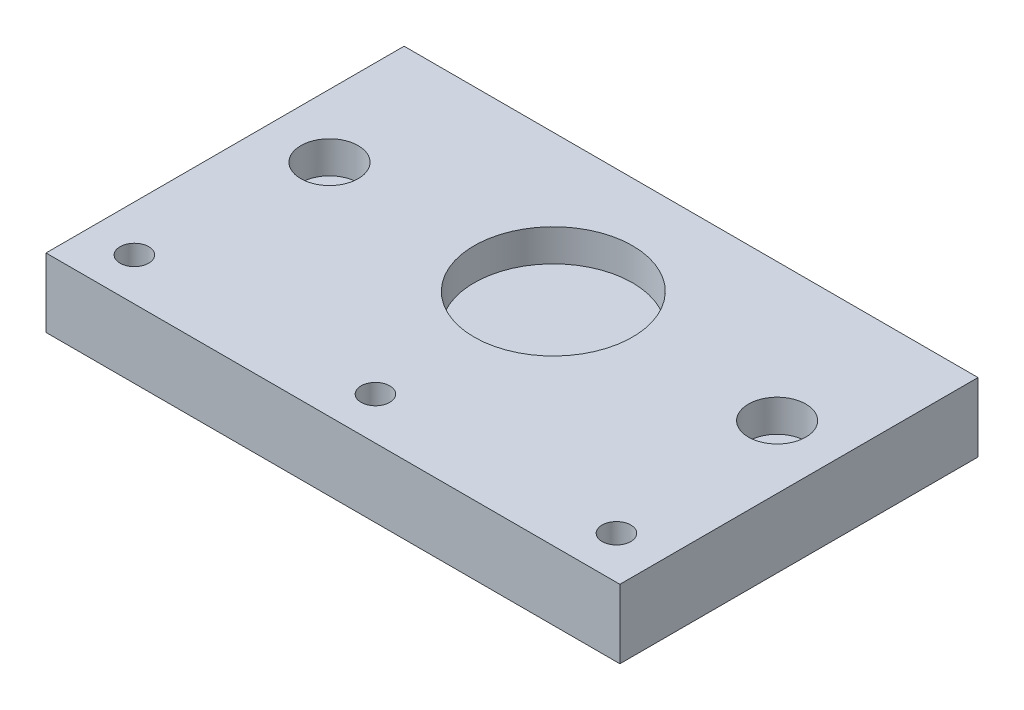
SolidWorks part; units mm, degrees
ref_plane "Front Plane" through (0, 0, 0) normal (0, 0, 1) x (1, 0, 0)
ref_plane "Top Plane" through (0, 0, 0) normal (0, 1, 0) x (1, 0, 0)
ref_plane "Right Plane" through (0, 0, 0) normal (1, 0, 0) x (0, 0, -1)
sketch "Sketch1" plane through (0, 0, 0) normal (0, 0, 1) x (1, 0, 0)
  line L1 (-31.75, 12.7) -> (31.75, 12.7)
  line L2 (-31.75, 12.7) -> (-31.75, -12.7)
  line L3 (-31.75, -12.7) -> (31.75, -12.7)
  line L4 (31.75, 12.7) -> (31.75, -12.7)
  point P4 (-31.75, 0)
  point P6 (0, 12.7)
  dimension "D1" = 63.5
  dimension "D2" = 25.4
extrude "Boss-Extrude1" add sketch "Sketch1" along normal blind 38.1
sketch "Sketch2" plane through (0, -12.7, 0) normal (0, -1, 0) x (1, 0, 0)
  line L0 (0, 0) -> (0, 102.7115) construction
  line L1 (-31.75, 0) -> (31.75, 0) construction
  circle A0 centre (24.765, 15.24) radius 3.175
  circle A1 centre (0, 15.24) radius 8.763
  circle A2 centre (-24.765, 15.24) radius 3.175
  dimension "D1" = 17.526
  dimension "D2" = 6.35
  dimension "D3" = 6.35
  dimension "D4" = 15.24
  dimension "D5" = 15.24
  dimension "D6" = 49.53
extrude "Cut-Extrude1" cut sketch "Sketch2" against normal blind 12.7 contours A2 | A0 region at (-24.765, -12.7, 15.24)
extrude "Cut-Extrude2" cut sketch "Sketch2<3>" against normal blind 4.826 contours A1
sketch "Sketch2<3>" plane through (0, -12.7, 0) normal (0, -1, 0) x (1, 0, 0) same geometry as "Sketch2"
sketch "Sketch3" plane through (0, -7.874, 0) normal (0, -1, 0) x (1, 0, 0)
  circle A0 centre (0, 15.24) radius 6.35
  dimension "D1" = 12.7
extrude "Cut-Extrude3" cut sketch "Sketch3" against normal up to vertex (20.574 mm away) up to point (31.75, 12.7, 0)
sketch "Sketch4" plane through (0, 12.7, 0) normal (0, 1, 0) x (1, 0, 0)
  line L0 (31.75, 0) -> (-31.75, 0) construction
  circle A0 centre (0, -15.24) radius 10.795
  point P6 (0, 0)
  dimension "D1" = 21.59
extrude "Cut-Extrude4" cut sketch "Sketch4" against normal blind 19.05
sketch "Sketch5" plane through (0, 12.7, 0) normal (0, 1, 0) x (1, 0, 0)
  line L0 (31.75, -38.1) -> (-31.75, -38.1) construction
  circle A0 centre (-26.67, -34.925) radius 1.5875
  circle A1 centre (0, -34.925) radius 1.5875
  circle A2 centre (26.67, -34.925) radius 1.5875
  dimension "D1" = 3.175
  dimension "D2" = 53.34
  dimension "D3" = 26.67
  dimension "D4" = 3.175
extrude "Cut-Extrude5" cut sketch "Sketch5" against normal blind 50.8
sketch "Sketch6" plane through (0, 0, 38.1) normal (0, 0, 1) x (1, 0, 0)
  line L0 (31.75, -12.7) -> (31.75, 12.7) construction
  line L1 (-31.75, -12.7) -> (31.75, -12.7)
  line L2 (-31.75, -12.7) -> (-31.75, -11.43)
  line L3 (-31.75, -11.43) -> (31.75, -11.43)
  line L4 (31.75, -12.7) -> (31.75, -11.43)
  dimension "D1" = 1.27
extrude "Cut-Extrude6" cut sketch "Sketch6" against normal up to vertex (38.1 mm away) up to point (-31.75, -12.7, 0)
sketch "Sketch7" plane through (0, 0, 38.1) normal (0, 0, 1) x (1, 0, 0)
  line L4 (-31.75, -11.43) -> (31.75, -11.43)
  line L5 (31.75, -11.43) -> (31.75, 12.7)
  line L6 (31.75, 12.7) -> (-31.75, 12.7)
  line L7 (-31.75, 12.7) -> (-31.75, -11.43)
  line L8 (-31.75, -11.43) -> (31.75, -11.43)
  line L9 (31.75, -11.43) -> (31.75, 12.7)
  line L10 (31.75, 12.7) -> (-31.75, 12.7)
  line L11 (-31.75, 12.7) -> (-31.75, -11.43)
  dimension "D1" = 0
extrude "Boss-Extrude2" add sketch "Sketch7" along normal blind 1.524
sketch "Sketch8" plane through (0, -6.35, 0) normal (0, 1, 0) x (1, 0, 0)
  line L1 (-42.4868, 12.7569) -> (52.6567, 12.7569)
  line L2 (-42.4868, 12.7569) -> (-42.4868, -56.416)
  line L3 (-42.4868, -56.416) -> (52.6567, -56.416)
  line L4 (52.6567, 12.7569) -> (52.6567, -56.416)
extrude "Cut-Extrude7" cut sketch "Sketch8" along normal through all
sketch "Sketch9" plane through (0, -11.43, 0) normal (0, -1, 0) x (1, 0, 0)
  line L4 (31.75, 0) -> (31.75, 39.624)
  line L5 (31.75, 39.624) -> (-31.75, 39.624)
  line L6 (-31.75, 39.624) -> (-31.75, 0)
  line L7 (-31.75, 0) -> (31.75, 0)
  line L8 (31.75, 0) -> (31.75, 39.624)
  line L9 (31.75, 39.624) -> (-31.75, 39.624)
  line L10 (-31.75, 39.624) -> (-31.75, 0)
  line L11 (-31.75, 0) -> (31.75, 0)
  circle A0 centre (26.67, 34.925) radius 1.5875 construction
  circle A1 centre (0, 34.925) radius 1.5875 construction
  circle A2 centre (-26.67, 34.925) radius 1.5875 construction
  circle A3 centre (-24.765, 15.24) radius 3.175 construction
  circle A4 centre (0, 15.24) radius 8.763 construction
  circle A5 centre (24.765, 15.24) radius 3.175 construction
  circle A6 centre (26.67, 34.925) radius 1.5875
  circle A7 centre (0, 34.925) radius 1.5875
  circle A8 centre (-26.67, 34.925) radius 1.5875
  circle A9 centre (-24.765, 15.24) radius 3.175
  circle A10 centre (0, 15.24) radius 8.763
  circle A11 centre (24.765, 15.24) radius 3.175
  dimension "D1" = 0
extrude "Boss-Extrude3" add sketch "Sketch9" along normal blind 2.54
sketch "Sketch10" plane through (0, -13.97, 0) normal (0, -1, 0) x (1, 0, 0)
  circle A0 centre (0, 15.24) radius 6.35 construction
  circle A1 centre (0, 15.24) radius 6.35
  circle A3 centre (0, 15.24) radius 8.763
  circle A4 centre (0, 15.24) radius 8.763
  dimension "D1" = 0
extrude "Cut-Extrude9" cut sketch "Sketch10" against normal through all
sketch "Sketch11" plane through (0, -13.97, 0) normal (0, -1, 0) x (1, 0, 0)
  circle A0 centre (0, 15.24) radius 8.763 construction
  circle A1 centre (0, 15.24) radius 8.763
  circle A2 centre (24.765, 15.24) radius 3.175 construction
  circle A3 centre (-24.765, 15.24) radius 3.175 construction
  circle A4 centre (24.765, 15.24) radius 3.175
  circle A5 centre (-24.765, 15.24) radius 3.175
extrude "Boss-Extrude5" add sketch "Sketch11" against normal blind 4.064
